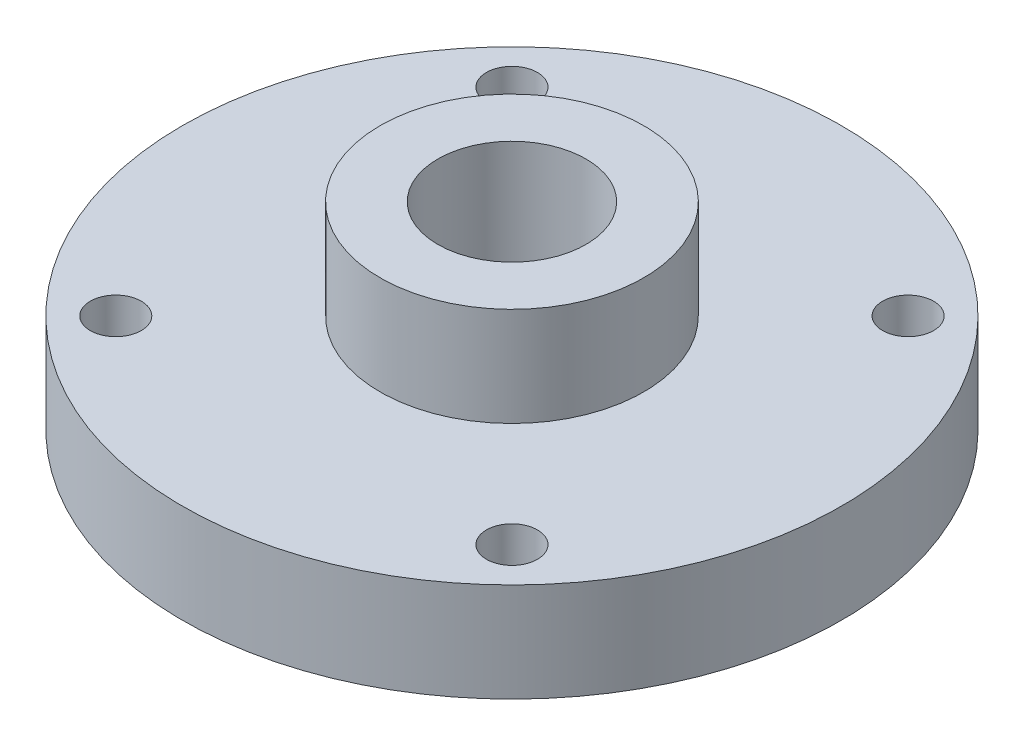
SolidWorks part; units mm, degrees
material "6061-T6 (SS)"
ref_plane "Front Plane" through (0, 0, 0) normal (0, 0, 1) x (1, 0, 0)
ref_plane "Top Plane" through (0, 0, 0) normal (0, 1, 0) x (1, 0, 0)
ref_plane "Right Plane" through (0, 0, 0) normal (1, 0, 0) x (0, 0, -1)
sketch "Sketch1" plane through (0, 0, 0) normal (0, 0, 1) x (1, 0, 0)
  line L0 (0, 0) -> (0, -19.05) construction
  line L6 (-12.7, -15.875) -> (-12.7, -19.05)
  line L7 (-12.7, 0) -> (-12.7, -9.525)
  line L8 (-12.7, -9.525) -> (-31.75, -9.525)
  line L9 (-31.75, -9.525) -> (-31.75, -19.05)
  line L15 (-19.0373, -19.05) -> (-12.7, -19.05)
  line L17 (-31.75, -19.05) -> (-23.8125, -19.05)
  line L18 (-23.8125, -19.05) -> (-23.8125, -15.9131)
  line L19 (-23.8125, -15.9131) -> (-19.0373, -15.9131)
  line L20 (-19.0373, -15.9131) -> (-19.0373, -19.05)
  line L21 (-12.7, 0) -> (0, 0)
  line L22 (0, 0) -> (0, -15.875)
  line L23 (0, -15.875) -> (-12.7, -15.875)
  point P1 (0, 0)
  point P12 (0, -26.5817)
  point P13 (0, 0)
  dimension "D2" = 25.4
  dimension "D3" = 9.525
  dimension "D4" = 25.4
  dimension "D5" = 3.175
  dimension "D7" = 63.5
  dimension "D8" = 15.875
  dimension "D9" = 4.7752
  dimension "D12" = 47.625
  dimension "D13" = 3.1369
revolve "Revolve1" add sketch "Sketch1" angle 360 about L0
hole_wizard "#10 (0.1935) Diameter Hole1" positions "Sketch2" profile "Sketch3" hole size "#10" standard "ANSI Inch" end condition through all
sketch "Sketch2" plane through (0, 0, 0) normal (0, 1, 0) x (1, 0, 0)
  line L0 (-19.083, 19.083) -> (19.083, -19.083) construction
  line L2 (19.083, 19.083) -> (-19.083, -19.083) construction
  line L3 (0, 0) -> (-24.6236, 0) construction
  point P0 (19.083, 19.083)
  point P2 (-19.083, 19.083)
  point P4 (-19.083, -19.083)
  point P6 (19.083, -19.083)
  dimension "D1" = 53.975
  dimension "D2" = 45
sketch "Sketch3" plane through (19.083, 0, -19.083) normal (1, 0, 0) x (0, 0, 1)
  line L0 (0, 0) -> (0, 19.05)
  line L1 (0, 19.05) -> (2.4574, 19.05)
  line L2 (2.4574, 19.05) -> (2.4574, 0)
  line L5 (2.4574, 0) -> (0, 0)
  line L11 (0, -6.35) -> (0, 107.95) construction
  dimension "Thru Hole Dia." = 4.9149
  dimension "Thru Hole Depth" = 19.05
hole_wizard "Pipe Tap Drill for 3/8 Tap1" positions "3DSketch1" profile "Sketch4" hole size "3/8" standard "ANSI Inch" end condition through all
sketch3d "3DSketch1"
  circle A1 centre (0, 0, 0) radius 12.7 construction
  point P0 (0, 0, 0)
  point P9 (0, 12.7, 0)
sketch "Sketch4" plane through (0, 0, 0) normal (1, 0, 0) x (0, 0, 1)
  line L0 (0, 0) -> (0, 19.05)
  line L1 (0, 19.05) -> (7.1374, 19.05)
  line L2 (7.1374, 19.05) -> (7.1374, 0)
  line L5 (7.1374, 0) -> (0, 0)
  line L11 (0, -6.35) -> (0, 107.95) construction
  dimension "Thru Hole Dia." = 14.2748
  dimension "Thru Hole Depth" = 19.05
